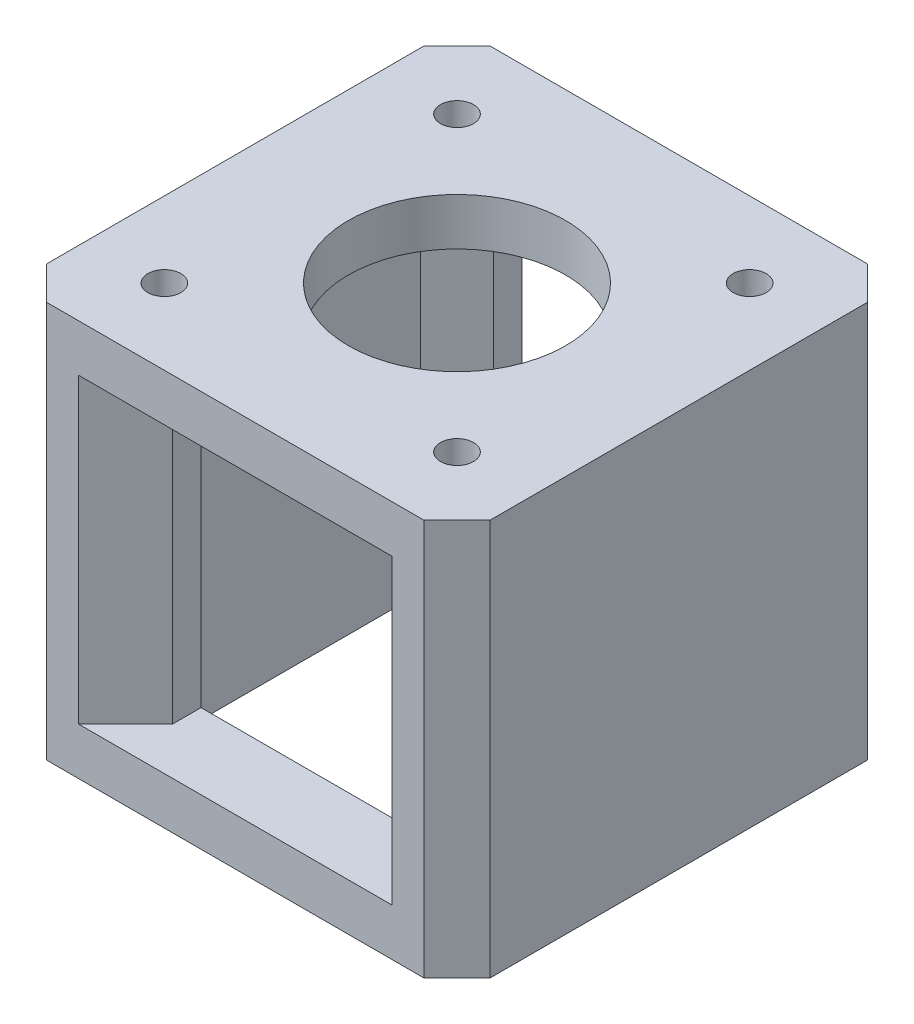
SolidWorks part; units mm, degrees
ref_plane "Front Plane" through (0, 0, 0) normal (0, 0, 1) x (1, 0, 0)
ref_plane "Top Plane" through (0, 0, 0) normal (0, 1, 0) x (1, 0, 0)
ref_plane "Right Plane" through (0, 0, 0) normal (1, 0, 0) x (0, 0, -1)
sketch "Sketch1" plane through (0, 0, 0) normal (0, 1, 0) x (1, 0, 0)
  line L0 (8, 39) -> (39, 39) construction
  line L1 (0, 0) -> (47, 0)
  line L2 (0, 0) -> (0, 47)
  line L3 (0, 47) -> (47, 47)
  line L4 (47, 0) -> (47, 47)
  line L5 (39, 39) -> (39, 8) construction
  line L6 (11.8891, 47) -> (11.8891, 39)
  line L7 (11.8891, 39) -> (8, 35.1109)
  line L8 (8, 35.1109) -> (0, 35.1109)
  line L9 (23.5, 47) -> (23.5, 0) construction
  line L10 (0, 23.5) -> (47, 23.5) construction
  line L11 (35.1109, 47) -> (35.1109, 39)
  line L12 (35.1109, 39) -> (39, 35.1109)
  line L13 (39, 35.1109) -> (47, 35.1109)
  line L14 (47, 11.8891) -> (39, 11.8891)
  line L15 (39, 11.8891) -> (35.1109, 8)
  line L16 (35.1109, 8) -> (35.1109, 0)
  line L17 (11.8891, 0) -> (11.8891, 8)
  line L18 (11.8891, 8) -> (8, 11.8891)
  line L19 (8, 11.8891) -> (0, 11.8891)
  line L20 (11.8891, 39) -> (35.1109, 39)
  line L21 (35.1109, 8) -> (11.8891, 8)
  line L22 (39, 11.8891) -> (39, 35.1109)
  line L23 (8, 35.1109) -> (8, 11.8891)
  circle A0 centre (8, 39) radius 1.75
  circle A1 centre (39, 39) radius 1.75
  circle A2 centre (39, 8) radius 1.75
  circle A3 centre (8, 8) radius 1.75
  circle A4 centre (23.5, 23.5) radius 11.5
  point P13 (39, 23.5)
  point P14 (47, 23.5)
  point P15 (23.5, 39)
  point P16 (23.5, 47)
  dimension "D3" = 3.5
  dimension "D6" = 23
  dimension "D1" = 8
  dimension "D2" = 31
  dimension "D4" = 135
  dimension "D5" = 2.75
extrude "Boss-Extrude1" add sketch "Sketch1" along normal blind 5 contours L8 L7 L6 L3 L2 A0 | L23 L8 L2 L19 | L18 L19 L2 L1 L17 A3 | L16 L21 L17 L1 | L15 L16 L1 L4 L14 A2 | L22 L14 L4 L13 | L12 L13 L4 L3 L11 A1 | L6 L20 L11 L3 region at (5.5022, 0, -5.5022) region at (23.5, 0, -4) region at (4, 0, -23.5) region at (41.4978, 0, -5.5022) region at (5.5022, 0, -41.4978) region at (43, 0, -23.5) region at (23.5, 0, -43) region at (41.4978, 0, -41.4978)
extrude "Boss-Extrude2" add sketch "Sketch1<3>" along normal blind 42 contours L18 L19 L2 L1 L17 A3 | L8 L7 L6 L3 L2 A0 | L12 L13 L4 L3 L11 A1 | L15 L16 L1 L4 L14 A2 | L23 L8 L2 L19 | L22 L14 L4 L13 region at (5.5022, 0, -5.5022) region at (4, 0, -23.5) region at (41.4978, 0, -5.5022) region at (5.5022, 0, -41.4978) region at (43, 0, -23.5) region at (41.4978, 0, -41.4978)
sketch "Sketch1<3>" plane through (0, 0, 0) normal (0, 1, 0) x (1, 0, 0) same geometry as "Sketch1"
extrude "Boss-Extrude3" add sketch "Sketch1<4>" against normal blind 5 from surface contours L7 L23 L18 L21 L15 L22 L12 L20 A4 | L6 L20 L11 L3 | L8 L7 L6 L3 L2 A0 | L23 L8 L2 L19 | L18 L19 L2 L1 L17 A3 | L16 L21 L17 L1 | L15 L16 L1 L4 L14 A2 | L22 L14 L4 L13 | L12 L13 L4 L3 L11 A1 region at (5.5022, 0, -5.5022) region at (23.5, 0, -4) region at (4, 0, -23.5) region at (41.4978, 0, -5.5022) region at (10.2545, 0, -10.2545) region at (5.5022, 0, -41.4978) region at (43, 0, -23.5) region at (23.5, 0, -43) region at (41.4978, 0, -41.4978) starting at face at (8, 42, -6.25)
sketch "Sketch1<4>" plane through (0, 0, 0) normal (0, 1, 0) x (1, 0, 0) same geometry as "Sketch1"
chamfer "Chamfer2" distance 5 angle 45 4 edges at (11.8891, 21, 0) (35.1109, 21, 0) (35.1109, 21, -47) (11.8891, 21, -47)
chamfer "Chamfer4" distance 3.5 4 edges at (47, 21, 0) (0, 21, 0) (0, 21, -47) (47, 21, -47)
